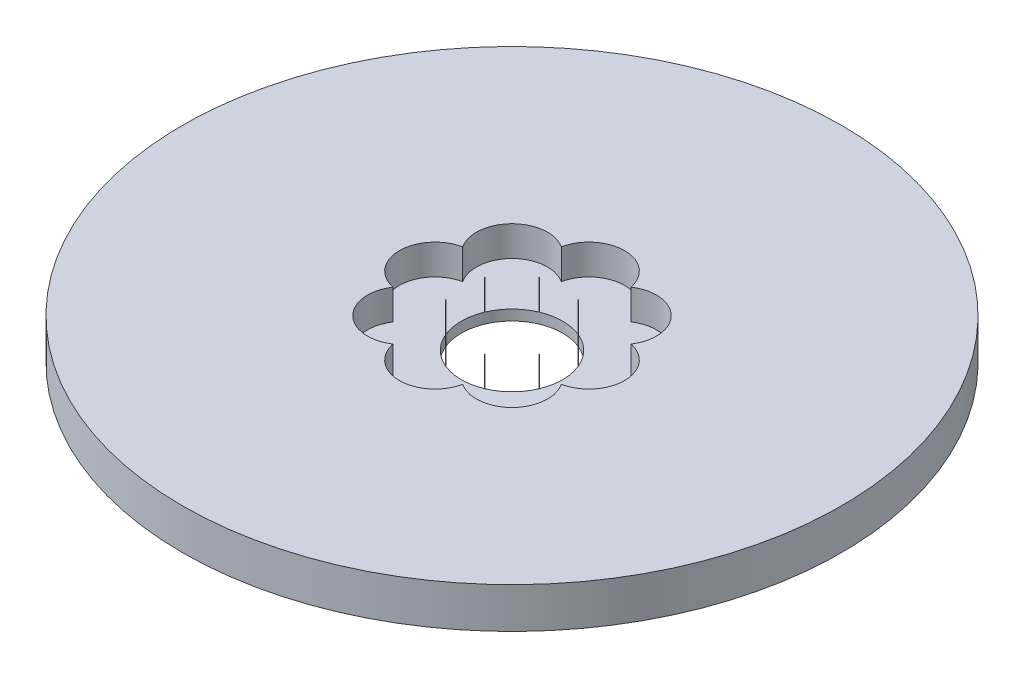
SolidWorks part; units mm, degrees
ref_plane "Front Plane" through (0, 0, 0) normal (0, 0, 1) x (1, 0, 0)
ref_plane "Top Plane" through (0, 0, 0) normal (0, 1, 0) x (1, 0, 0)
ref_plane "Right Plane" through (0, 0, 0) normal (1, 0, 0) x (0, 0, -1)
sketch "Sketch1" plane through (0, 0, 0) normal (0, 1, 0) x (1, 0, 0)
  circle A0 centre (0, 0) radius 65
  dimension "FLANGE_OD" = 130
extrude "Boss-Extrude1" add sketch "Sketch1" along normal blind 8
sketch "Sketch2" plane through (0, 0, 0) normal (0, 1, 0) x (1, 0, 0)
  circle A0 centre (0, 0) radius 10
  dimension "BORE_D" = 20
extrude "Cut-Extrude1" cut sketch "Sketch2" along normal through all
sketch "Sketch3" plane through (0, 8, 0) normal (0, 1, 0) x (1, 0, 0)
  circle A0 centre (0, 0) radius 15.1773 construction
  circle A1 centre (-15.1773, 0) radius 7.0266
  dimension "BOLT_D" = 14.0531
  dimension "BOLT_PCD" = 30.3546
extrude "Cut-Extrude2" cut sketch "Sketch3" against normal blind 5.9491
pattern_circular "CirPattern1" count 8 over 360 about axis through (0, 0, 0) along (0, 1, 0) of "Cut-Extrude2"
